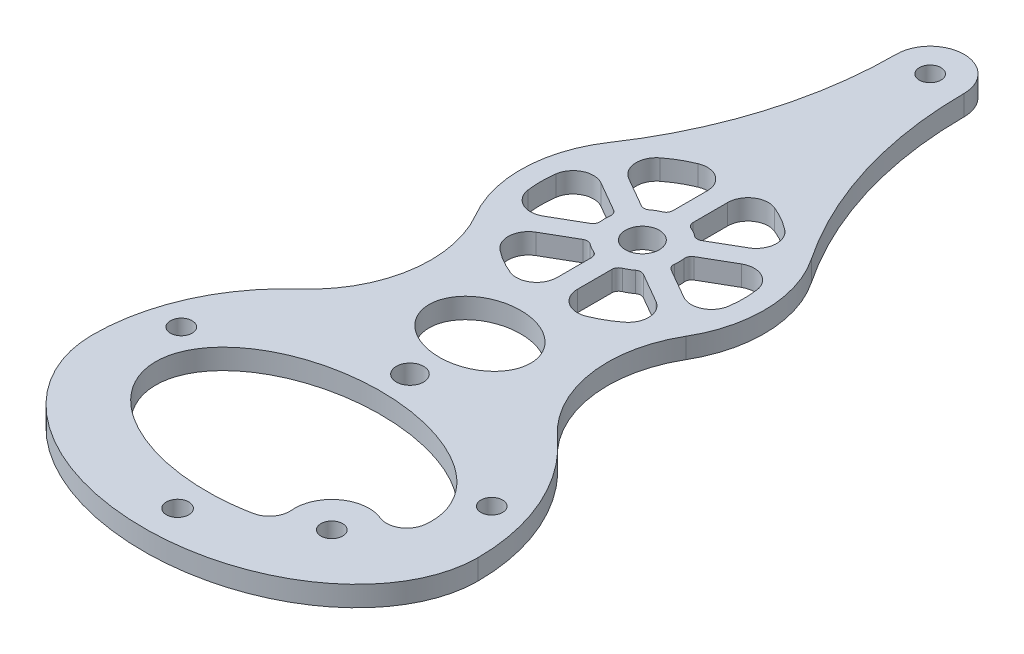
SolidWorks part; units mm, degrees
ref_plane "Front Plane" through (0, 0, 0) normal (0, 0, 1) x (1, 0, 0)
ref_plane "Top Plane" through (0, 0, 0) normal (0, 1, 0) x (1, 0, 0)
ref_plane "Right Plane" through (0, 0, 0) normal (1, 0, 0) x (0, 0, -1)
sketch "Sketch1" plane through (0, 0, 0) normal (0, 1, 0) x (1, 0, 0)
  line L0 (0, -1000) -> (0, 49000) construction
  arc A0 (-14.898, 10.0354) -> (-6.7072, 56.4165) centre (-63.0135, 42.4463) ccw construction
  arc A1 (-14.898, 10.0354) -> (-15.4999, -9.0782) centre (0, 0) ccw construction
  arc A2 (-19.0005, -31.5234) -> (-15.4999, -9.0782) centre (-30.9998, -18.1563) ccw construction
  arc A3 (-19.0005, -31.5234) -> (-28.4436, -52.6898) centre (0, -52.6898) ccw construction
  arc A4 (-14.898, 10.0354) -> (-6.7072, 56.4165) centre (-63.0135, 42.4463) ccw construction
  arc A5 (-14.898, 10.0354) -> (-15.4999, -9.0782) centre (0, 0) ccw
  arc A6 (-19.0005, -31.5234) -> (-15.4999, -9.0782) centre (-30.9998, -18.1563) ccw
  arc A7 (-19.0005, -31.5234) -> (-28.4436, -52.6898) centre (0, -52.6898) ccw
  arc A8 (-14.898, 10.0354) -> (-5, 42.4463) centre (-63.0135, 42.4463) ccw
  arc A9 (-5, 42.4463) -> (5, 42.4463) centre (0, 42.4463) cw
  arc A10 (14.898, 10.0354) -> (5, 42.4463) centre (63.0135, 42.4463) cw
  arc A11 (14.898, 10.0354) -> (15.4999, -9.0782) centre (0, 0) cw
  arc A12 (19.0005, -31.5234) -> (15.4999, -9.0782) centre (30.9998, -18.1563) cw
  arc A13 (19.0005, -31.5234) -> (28.4436, -52.6898) centre (0, -52.6898) cw
  circle A14 centre (22.8961, -45.1123) radius 1.6 construction
  circle A15 centre (-22.8961, -45.1123) radius 1.6 construction
  circle A16 centre (22.8961, -45.1123) radius 1.6
  circle A17 centre (-22.8961, -45.1123) radius 1.6
  circle A18 centre (0, 0) radius 2.5
  circle A19 centre (0, 42.4463) radius 1.6 construction
  circle A20 centre (0, 42.4463) radius 1.6
  circle A21 centre (0, -68.5564) radius 1.65 construction
  circle A22 centre (0, -34.2782) radius 2.0153 construction
  circle A23 centre (0, -68.5564) radius 1.65
  circle A24 centre (0, -34.2782) radius 2.0153
  ellipse E0 centre (0, -52.6898) end of major axis (-28.4436, -52.6898) minor radius 20.8666 (-28.4436, -52.6898) -> (28.4436, -52.6898) ccw construction
  ellipse E1 centre (0, -52.6898) end of major axis (-28.4436, -52.6898) minor radius 20.8666 (-28.4436, -52.6898) -> (28.4436, -52.6898) ccw
  ellipse E2 centre (0, -51.4173) end of major axis (20.3628, -51.4173) minor radius 12.813 construction
  ellipse E3 centre (0, -23.9574) end of major axis (-7.5, -23.9574) minor radius 5.9947 construction
  ellipse E4 centre (0, -51.4173) end of major axis (20.3628, -51.4173) minor radius 12.813
  ellipse E5 centre (0, -23.9574) end of major axis (-7.5, -23.9574) minor radius 5.9947
  dimension "D1" = 5
extrude "Boss-Extrude1" add sketch "Sketch1" along normal blind 3
sketch "Sketch2" plane through (0, 0, 0) normal (0, -1, 0) x (1, 0, 0)
  circle A0 centre (14.1202, 59.9265) radius 5.5
  circle A1 centre (14.1202, 59.9265) radius 8.2743 construction
  dimension "D1" = 11
extrude "Boss-Extrude2" add sketch "Sketch2" against normal up to surface (3 mm away) up to face at (0, 3, 70.2064)
fillet "Fillet1" radius 3 2 edges at (18.5629, 1.5, 56.6842) (9.417, 1.5, 62.7778)
sketch "Sketch3" plane through (0, 3, 0) normal (0, 1, 0) x (1, 0, 0)
  circle A0 centre (14.1202, -59.9265) radius 1.6
  circle A1 centre (14.1202, -59.9265) radius 5.5 construction
  dimension "D1" = 3.2
extrude "Cut-Extrude1" cut sketch "Sketch3" against normal through all
sketch "Sketch4" plane through (0, 3, 0) normal (0, 1, 0) x (1, 0, 0)
  line L0 (-1.5, -5.2915) -> (-1.5, -14.8874)
  line L1 (-5.1157, -8.8606) -> (5.1157, -8.8606) construction
  line L2 (5.1157, -8.8606) -> (10.2314, 0) construction
  line L3 (10.2314, 0) -> (5.1157, 8.8606) construction
  line L4 (5.1157, 8.8606) -> (-5.1157, 8.8606) construction
  line L5 (-5.1157, 8.8606) -> (-10.2314, 0) construction
  line L6 (-10.2314, 0) -> (-5.1157, -8.8606) construction
  line L7 (0, -201000) -> (0, 249000) construction
  line L8 (0, 0) -> (-5.1157, -8.8606) construction
  line L9 (-3.8326, -3.9448) -> (-12.1428, -8.7427)
  circle A0 centre (0, 0) radius 8.8606 construction
  circle A1 centre (0, 0) radius 2.5 construction
  circle A2 centre (-5.1157, -8.8606) radius 7.7314 construction
  circle A3 centre (-5.1157, -8.8606) radius 4.7314 construction
  arc A4 (-1.5, -5.2915) -> (-3.8326, -3.9448) centre (0, 0) cw
  circle A5 centre (0, 0) radius 17.9627 construction
  arc A6 (-14.898, 10.0354) -> (-15.4999, -9.0782) centre (0, 0) ccw construction
  arc A7 (-1.5, -14.8874) -> (-12.1428, -8.7427) centre (0, 0) cw
  dimension "D2" = 1.5
  dimension "D1" = 3
extrude "Cut-Extrude2" cut sketch "Sketch4" against normal through all
fillet "Fillet2" radius 3 2 edges at (-1.5, 1.5, 14.8874) (-12.1428, 1.5, 8.7427)
fillet "Fillet3" radius 1 2 edges at (-1.5, 1.5, 5.2915) (-3.8326, 1.5, 3.9448)
pattern_circular "CirPattern1" count 6 over 360 about axis through (0, 3, 0) along (0, -1, 0) of "Fillet2", "Cut-Extrude2", "Fillet3"
